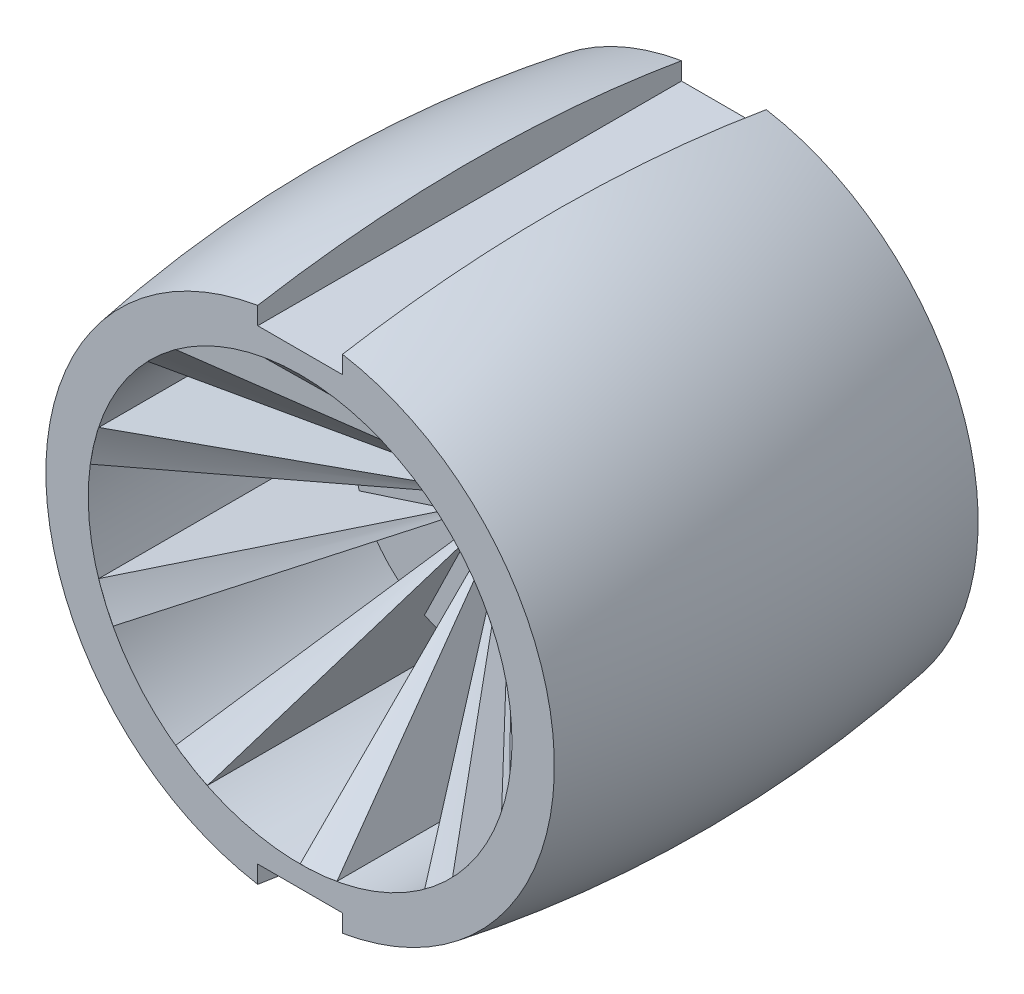
SolidWorks part; units mm, degrees
ref_plane "Front Plane" through (0, 0, 0) normal (0, 0, 1) x (1, 0, 0)
ref_plane "Top Plane" through (0, 0, 0) normal (0, 1, 0) x (1, 0, 0)
ref_plane "Right Plane" through (0, 0, 0) normal (1, 0, 0) x (0, 0, -1)
sketch "Sketch1" plane through (0, 0, 0) normal (1, 0, 0) x (0, 0, -1)
  line L0 (0, 0) -> (0, 50) construction
  line L1 (-19.054, 30) -> (21.2337, 30) construction
  line L2 (-25, 30) -> (-25, 25)
  line L3 (-25, 25) -> (25, 25)
  line L4 (25, 25) -> (25, 30)
  arc A0 (-25, 30) -> (25, 30) centre (0, -117.902) cw
  dimension "D3" = 150
  dimension "D1" = 50
  dimension "D2" = 30
  dimension "D4" = 25
  dimension "D5" = 25
  dimension "D6" = 5
sketch "Sketch2" plane through (0, 0, 0) normal (0, 0, 1) x (1, 0, 0)
  circle A0 centre (0, 0) radius 30 construction
  dimension "D1" = 60
sketch "Sketch3" plane through (0, 0, 0) normal (0, 0, 1) x (1, 0, 0)
  circle A0 centre (0, 0) radius 30
  dimension "D1" = 60
sweep "Sweep1" add profiles "Sketch1" path "Sketch3"
sketch "Sketch4" plane through (0, 0, 0) normal (0, 0, 1) x (1, 0, 0)
  circle A0 centre (0, 0) radius 3.75
  circle A1 centre (0, 0) radius 15
  dimension "D1" = 7.5
  dimension "D2" = 30
extrude "Boss-Extrude1" add sketch "Sketch4" along normal mid plane 7.5 separate body
sketch "Sketch5" plane through (0, 0, 0) normal (0, 1, 0) x (1, 0, 0)
  line L0 (0, 26.3312) -> (0, -26.1905) construction
sketch "Sketch6" plane through (0, 0, 0) normal (1, 0, 0) x (0, 0, -1)
  line L0 (-25, 25) -> (25, 25)
  line L1 (25, 25) -> (3.75, 3.75)
  line L2 (3.75, -15) -> (3.75, 15) construction
  line L4 (-3.75, 15) -> (-3.75, -15) construction
  line L5 (-3.75, 3.75) -> (-25, 25)
  line L6 (-3.75, 3.75) -> (-3.75, 15)
  line L7 (-3.75, 15) -> (3.75, 15)
  line L8 (3.75, 15) -> (3.75, 3.75)
  dimension "D1" = 45
  dimension "D2" = 45
revolve "Revolve1" add sketch "Sketch6" angle 10 about L0
pattern_circular "CirPattern1" count 10 over 360 about axis through (0, 0, -26.3312) along (0, 0, 1) of "Revolve1" reverse direction yes
sketch "Sketch7" plane through (0, 0, 0) normal (0, 0, 1) x (1, 0, 0)
  line L1 (-5, 35) -> (5, 35)
  line L2 (-5, 35) -> (-5, 27.5)
  line L3 (-5, 27.5) -> (5, 27.5)
  line L4 (5, 35) -> (5, 27.5)
  dimension "D1" = 27.5
  dimension "D2" = 10
  dimension "D3" = 5
  dimension "D4" = 7.5
extrude "Cut-Extrude1" cut sketch "Sketch7" against normal through all both and the other way through all
mirror "Mirror1" about plane through (0, 0, 0) normal (0, 1, 0) of "Cut-Extrude1"
